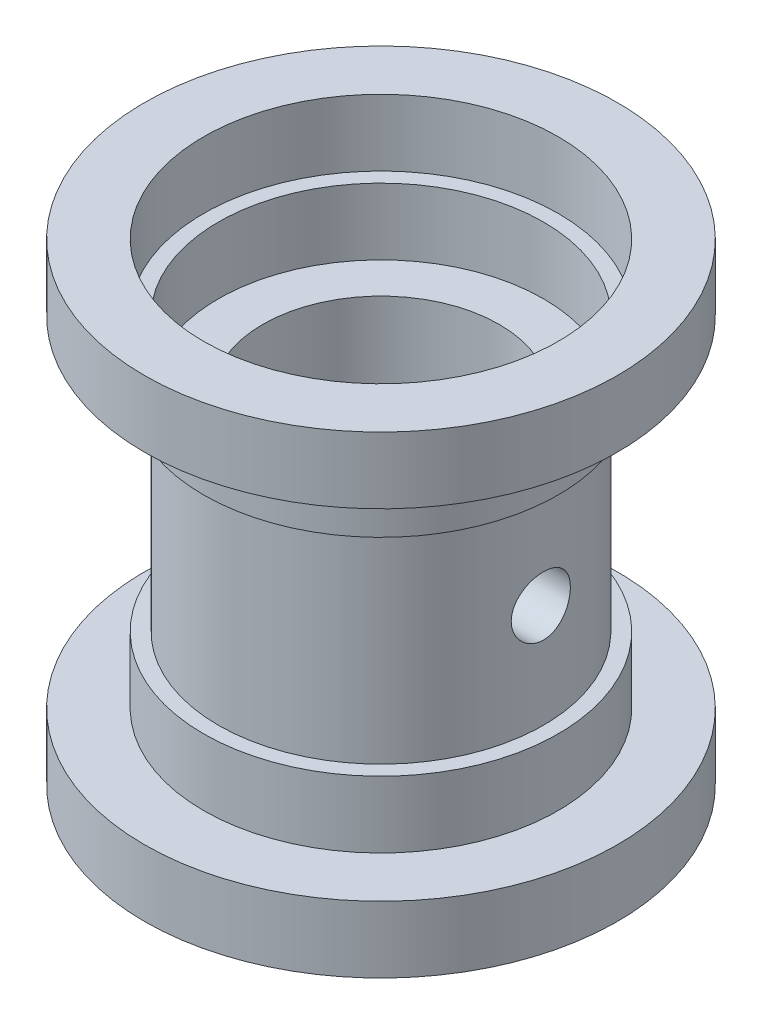
SolidWorks part; units mm, degrees
ref_plane "Front Plane" through (0, 0, 0) normal (0, 0, 1) x (1, 0, 0)
ref_plane "Top Plane" through (0, 0, 0) normal (0, 1, 0) x (1, 0, 0)
ref_plane "Right Plane" through (0, 0, 0) normal (1, 0, 0) x (0, 0, -1)
sketch "Sketch1" plane through (0, 0, 0) normal (0, 1, 0) x (1, 0, 0)
  circle A0 centre (0, 0) radius 22
  circle A1 centre (0, 0) radius 32
  circle A2 centre (0, 0) radius 24
  circle A3 centre (0, 0) radius 16
  dimension "D1" = 44
  dimension "D2" = 64
  dimension "D3" = 48
  dimension "D4" = 32
extrude "Boss-Extrude1" add sketch "Sketch1" along normal mid plane 28 contours A0 A3 region at (-21.3777, 0, 0)
extrude "Boss-Extrude3" add sketch "Sketch1<5>" against normal mid plane 46 contours A2 A0 region at (-23.3212, 0, 0)
sketch "Sketch1<5>" plane through (0, 0, 0) normal (0, 1, 0) x (1, 0, 0) same geometry as "Sketch1"
extrude "Boss-Extrude4" add sketch "Sketch1<6>" along normal mid plane 64 contours A1 A2 region at (-31.0949, 0, 0)
sketch "Sketch1<6>" plane through (0, 0, 0) normal (0, 1, 0) x (1, 0, 0) same geometry as "Sketch1"
extrude "Cut-Extrude1" cut sketch "Sketch1<7>" against normal mid plane 28 contours A2 A0 region at (-23.3212, 0, 0)
sketch "Sketch1<7>" plane through (0, 0, 0) normal (0, 1, 0) x (1, 0, 0) same geometry as "Sketch1"
extrude "Cut-Extrude2" cut sketch "Sketch1<8>" against normal mid plane 46 contours A1 A2 region at (-31.0949, 0, 0)
sketch "Sketch1<8>" plane through (0, 0, 0) normal (0, 1, 0) x (1, 0, 0) same geometry as "Sketch1"
sketch "Sketch2" plane through (0, 0, 0) normal (1, 0, 0) x (0, 0, -1)
  circle A0 centre (0, 0) radius 4
  dimension "D1" = 8
extrude "Cut-Extrude3" cut sketch "Sketch2" against normal mid plane 46
